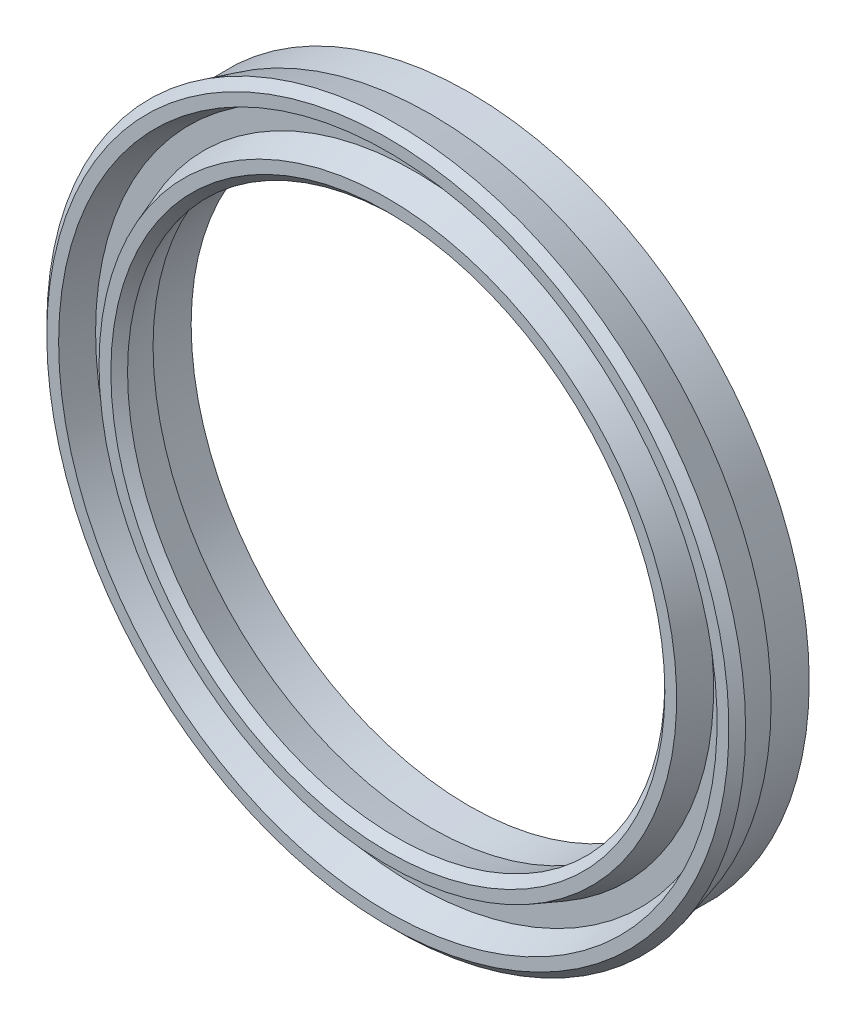
SolidWorks part; units mm, degrees
ref_plane "Front" through (0, 0, 0) normal (0, 0, 1) x (1, 0, 0)
ref_plane "Top" through (0, 0, 0) normal (0, 1, 0) x (1, 0, 0)
ref_plane "Right" through (0, 0, 0) normal (1, 0, 0) x (0, 0, -1)
sketch "Sketch1" plane through (-63.6, 0, -73.5571) normal (0, 1, 0) x (-1, 0, 0)
  line L0 (-63.6, 58.7571) -> (-63.6, 132.3142) construction
  line L1 (-114.2, 58.7571) -> (-125.5, 58.7571)
  line L2 (-125.5, 58.7571) -> (-125.5, 65.692)
  line L3 (-125.5, 65.692) -> (-127.2, 72.0365)
  line L4 (-127.2, 72.0365) -> (-125.6794, 73.5571)
  line L5 (-125.6794, 73.5571) -> (-123.5289, 73.5571)
  line L6 (-123.5289, 73.5571) -> (-121.7333, 68.6238)
  line L7 (-121.7333, 68.6238) -> (-117.9667, 68.6238)
  line L8 (-119.85, 68.6238) -> (-119.85, 58.7571) construction
  line L9 (-116.1711, 73.5571) -> (-117.9667, 68.6238)
  line L10 (-114.0206, 73.5571) -> (-116.1711, 73.5571)
  line L11 (-112.5, 72.0365) -> (-114.0206, 73.5571)
  line L12 (-114.2, 65.692) -> (-112.5, 72.0365)
  line L13 (-114.2, 58.7571) -> (-114.2, 65.692)
  dimension "D5" = 45
  dimension "D6" = 120
  dimension "D7" = 9.8667
  dimension "D8" = 3.7667
  dimension "D9" = 70
revolve "Body" add sketch "Sketch1" angle 360 about L0
equation "\"D7@Sketch1\" = \"h@Sketch1\" * 2 / 3"
equation "\"D8@Sketch1\" = \"s1@Sketch1\" / 3"
